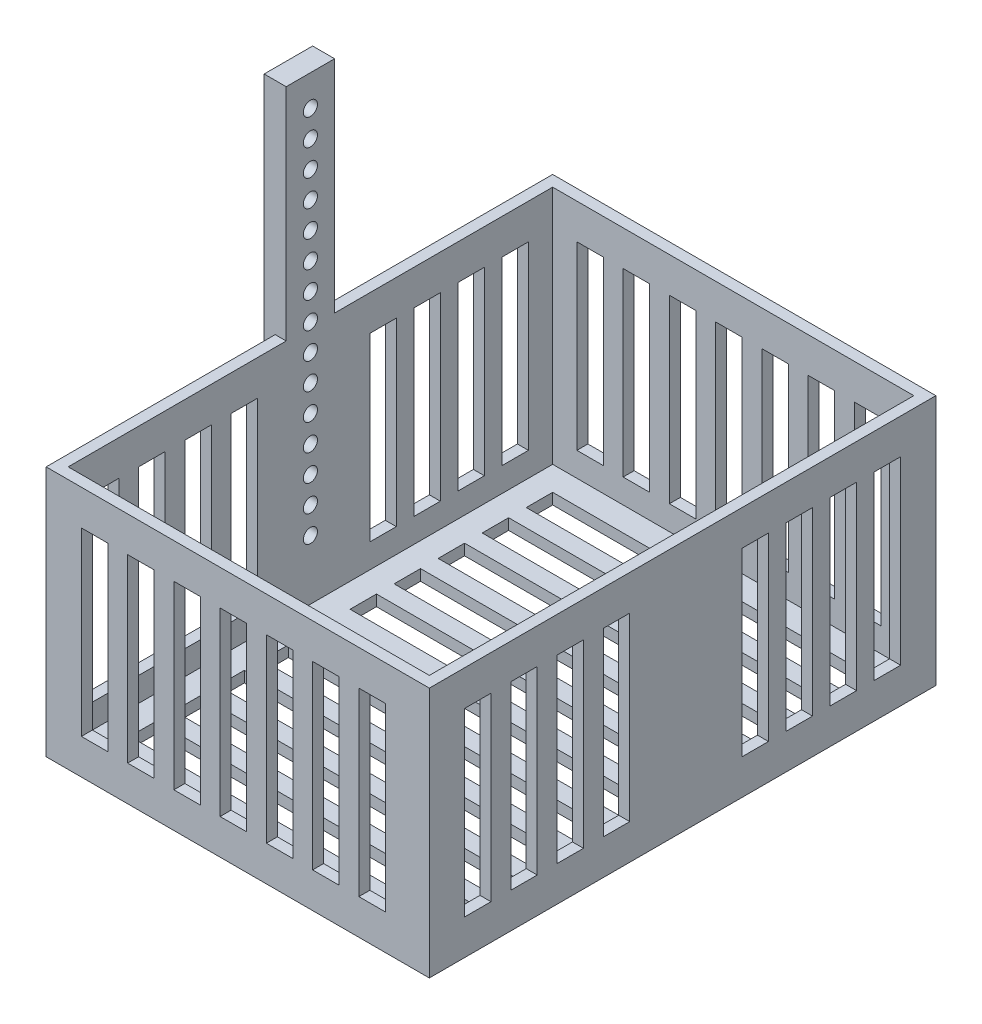
SolidWorks part; units mm, degrees
ref_plane "Front Plane" through (0, 0, 0) normal (0, 0, 1) x (1, 0, 0)
ref_plane "Top Plane" through (0, 0, 0) normal (0, 1, 0) x (1, 0, 0)
ref_plane "Right Plane" through (0, 0, 0) normal (1, 0, 0) x (0, 0, -1)
sketch "Sketch1" plane through (0, 0, 0) normal (0, 1, 0) x (1, 0, 0)
  line L1 (-43.5, 57.5) -> (43.5, 57.5)
  line L2 (-43.5, 57.5) -> (-43.5, -57.5)
  line L3 (-43.5, -57.5) -> (43.5, -57.5)
  line L4 (43.5, 57.5) -> (43.5, -57.5)
  point P4 (0, 57.5)
  point P6 (-43.5, 0)
  dimension "D1" = 87
  dimension "D2" = 115
extrude "Boss-Extrude1" add sketch "Sketch1" against normal blind 2.5
sketch "Sketch2" plane through (0, 0, 0) normal (0, 1, 0) x (1, 0, 0)
  line L1 (-43.5, 57.5) -> (43.5, 57.5)
  line L2 (-43.5, 57.5) -> (-43.5, -57.5)
  line L3 (-43.5, -57.5) -> (43.5, -57.5)
  line L4 (43.5, 57.5) -> (43.5, -57.5)
  line L5 (41, -55) -> (-41, -55)
  line L6 (41, -55) -> (41, 55)
  line L7 (41, 55) -> (-41, 55)
  line L8 (-41, -55) -> (-41, 55)
  dimension "D1" = 2.5
  dimension "D2" = 2.5
  dimension "D3" = 2.5
  dimension "D4" = 2.5
extrude "Boss-Extrude2" add sketch "Sketch2" along normal blind 54.5
sketch "Sketch3" plane through (0, -2.5, 0) normal (0, -1, 0) x (1, 0, 0)
  line L0 (-41, -55) -> (-41, 55) construction
  line L1 (-41, -5.5) -> (-46, -5.5)
  line L2 (-41, -5.5) -> (-41, 5.5)
  line L3 (-41, 5.5) -> (-46, 5.5)
  line L4 (-46, -5.5) -> (-46, 5.5)
  point P6 (-41, 0)
  dimension "D1" = 11
  dimension "D2" = 5
extrude "Boss-Extrude3" add sketch "Sketch3" against normal through all
sketch "Sketch4" plane through (0, 54.5, 0) normal (0, 1, 0) x (1, 0, 0)
  line L0 (-41, 55) -> (-41, -55) construction
  line L1 (-46, 5.5) -> (-41, 5.5)
  line L2 (-46, 5.5) -> (-46, -5.5)
  line L3 (-46, -5.5) -> (-41, -5.5)
  line L4 (-41, 5.5) -> (-41, -5.5)
  line L5 (-43.5, -5.5) -> (-46, -5.5) construction
extrude "Boss-Extrude4" add sketch "Sketch4" along normal blind 50
sketch "Sketch5" plane through (-46, 0, 0) normal (-1, 0, 0) x (0, 0, 1)
  line L1 (5.5, -2.5) -> (-5.5, -2.5) construction
  circle A0 centre (0, 97.5) radius 1.6
  point P2 (0, 0)
  dimension "D1" = 3.2
  dimension "D2" = 100
extrude "Cut-Extrude1" cut sketch "Sketch5" against normal up to next
pattern_linear "LPattern1" count 15 spacing 6 along (0, -1, 0) of "Cut-Extrude1"
sketch "Sketch6" plane through (0, 0, 0) normal (0, 0, 1) x (1, 0, 0)
  line L0 (-43.5, -2.5) -> (-43.5, 54.5) construction
  line L1 (-35.5, 46.5) -> (-29.5, 46.5)
  line L2 (-35.5, 46.5) -> (-35.5, 5.5)
  line L3 (-35.5, 5.5) -> (-29.5, 5.5)
  line L4 (-29.5, 46.5) -> (-29.5, 5.5)
  line L5 (-43.5, 54.5) -> (43.5, 54.5) construction
  line L6 (-43.5, -2.5) -> (43.5, -2.5) construction
  dimension "D1" = 8
  dimension "D2" = 8
  dimension "D3" = 8
  dimension "D4" = 6
extrude "Cut-Extrude2" cut sketch "Sketch6" against normal through all both and the other way through all
pattern_linear "LPattern2" count 7 spacing 10.5 along (1, 0, 0) of "Cut-Extrude2"
sketch "Sketch7" plane through (0, 0, 0) normal (1, 0, 0) x (0, 0, -1)
  line L0 (-57.5, -2.5) -> (-57.5, 54.5) construction
  line L1 (-43.5, 46.5) -> (-49.5, 46.5)
  line L2 (-43.5, 46.5) -> (-43.5, 5.5)
  line L3 (-43.5, 5.5) -> (-49.5, 5.5)
  line L4 (-49.5, 46.5) -> (-49.5, 5.5)
  line L5 (-5.5, 54.5) -> (-57.5, 54.5) construction
  line L6 (-5.5, -2.5) -> (-57.5, -2.5) construction
  dimension "D1" = 8
  dimension "D2" = 8
  dimension "D3" = 6
  dimension "D4" = 8
extrude "Cut-Extrude3" cut sketch "Sketch7" along normal through all both and the other way through all
pattern_linear "LPattern3" count 4 spacing 10.5 along (0, 0, -1) of "Cut-Extrude3"
sketch "Sketch8" plane through (0, 0, 0) normal (1, 0, 0) x (0, 0, -1)
  line L0 (57.5, 54.5) -> (5.5, 54.5) construction
  line L1 (49.5, 46.5) -> (43.5, 46.5)
  line L2 (49.5, 46.5) -> (49.5, 5.5)
  line L3 (49.5, 5.5) -> (43.5, 5.5)
  line L4 (43.5, 46.5) -> (43.5, 5.5)
  line L5 (57.5, -2.5) -> (57.5, 54.5) construction
  line L6 (57.5, -2.5) -> (5.5, -2.5) construction
  dimension "D1" = 8
  dimension "D2" = 8
  dimension "D3" = 8
  dimension "D4" = 6
sketch "Sketch9" plane through (0, 0, 0) normal (0, 1, 0) x (1, 0, 0)
  line L0 (43.5, 57.5) -> (-43.5, 57.5) construction
  line L1 (-35.5, 49.5) -> (35.5, 49.5)
  line L2 (-35.5, 49.5) -> (-35.5, 43.5)
  line L3 (-35.5, 43.5) -> (35.5, 43.5)
  line L4 (35.5, 49.5) -> (35.5, 43.5)
  line L5 (-43.5, 57.5) -> (-43.5, 5.5) construction
  line L6 (43.5, -57.5) -> (43.5, 57.5) construction
  dimension "D1" = 8
  dimension "D2" = 8
  dimension "D3" = 8
  dimension "D4" = 6
extrude "Cut-Extrude4" cut sketch "Sketch8" against normal through all both and the other way through all
pattern_linear "LPattern4" count 4 spacing 10 along (0, 0, 1) of "Cut-Extrude4"
extrude "Cut-Extrude5" cut sketch "Sketch9" against normal through all both
pattern_linear "LPattern5" count 10 spacing 10 along (0, 0, 1) of "Cut-Extrude5"
equation "\"wall\"=2.5"
equation "\"D1@Sketch2\"=\"wall\""
equation "\"D2@Sketch2\"=\"wall\""
equation "\"D3@Sketch2\"=\"wall\""
equation "\"D4@Sketch2\"=\"wall\""
equation "\"D1@Boss-Extrude2\"=57-\"wall\""
